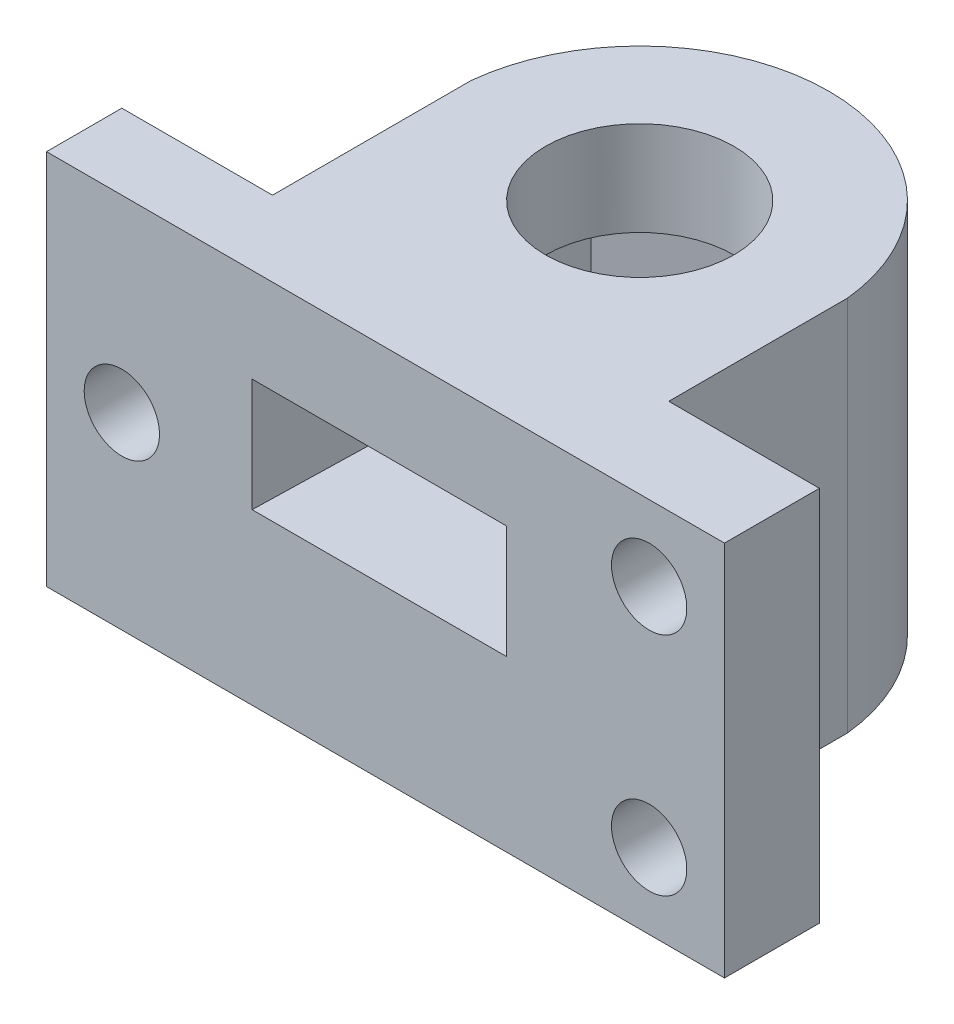
SolidWorks part; units mm, degrees
material "Copper"
ref_plane "Front Plane" through (0, 0, 0) normal (0, 0, 1) x (1, 0, 0)
ref_plane "Top Plane" through (0, 0, 0) normal (0, 1, 0) x (1, 0, 0)
ref_plane "Right Plane" through (0, 0, 0) normal (1, 0, 0) x (0, 0, -1)
sketch "Sketch1" plane through (0, 0, 0) normal (0, 1, 0) x (1, 0, 0)
  line L0 (0, 0) -> (20, 0)
  line L1 (0, 14.54) -> (0, 4)
  line L2 (20, 5.04) -> (20, 14.54)
  line L3 (0, 0) -> (-8, 0)
  line L4 (-8, 0) -> (-8, 4)
  line L5 (-8, 4) -> (0, 4)
  line L6 (20, 0) -> (28, 0)
  line L7 (28, 0) -> (28, 5.04)
  line L8 (28, 5.04) -> (20, 5.04)
  circle A0 centre (10, 13.5) radius 5
  arc A1 (0, 14.54) -> (20, 14.54) centre (10, 13.5) cw
  dimension "D1" = 13.5
  dimension "D2" = 9.5
  dimension "D3" = 10
extrude "Boss-Extrude1" add sketch "Sketch1" along normal blind 20
ref_plane "Plane1" through (0, 15, 0) normal (0, 1, 0) x (1, 0, 0)
sketch "Sketch4" plane through (0, 15, 0) normal (0, 1, 0) x (1, 0, 0)
  line L0 (10, 13.5) -> (10, -3.0938) construction
  line L2 (9.8055, 5.7082) -> (16.6507, 9.4357)
  line L3 (16.6507, 9.4357) -> (16.8451, 17.2275)
  line L4 (16.8451, 17.2275) -> (10.1945, 21.2918)
  line L5 (10.1945, 21.2918) -> (3.3493, 17.5643)
  line L6 (3.3493, 17.5643) -> (3.1549, 9.7725)
  line L7 (3.1549, 9.7725) -> (9.8055, 5.7082)
  circle A0 centre (10, 13.5) radius 6.75 construction
extrude "Cut-Extrude2" cut sketch "Sketch4" against normal blind 6
sketch "Sketch9" plane through (0, 0, -5.04) normal (0, 0, -1) x (-1, 0, 0)
  line L0 (-28, 20) -> (-28, 0) construction
  line L1 (-28, 0) -> (-20, 0) construction
  line L2 (-28, 20) -> (-20, 20) construction
  line L3 (8, 20) -> (8, 0) construction
  line L4 (0, 20) -> (8, 20) construction
  circle A0 centre (-24, 4) radius 2
  circle A1 centre (-24, 16) radius 2
  circle A2 centre (4, 10) radius 2
  dimension "D1" = 4
  dimension "D5" = 4
  dimension "D2" = 4
  dimension "D3" = 4
  dimension "D4" = 4
  dimension "D6" = 10
extrude "Cut-Extrude4" cut sketch "Sketch9" against normal blind 6
ref_plane "Plane7" through (0.2457, 0, -9.8451) normal (0.025, 0, -0.9997) x (-0.9997, 0, -0.025)
sketch "Sketch10" plane through (0.2457, 0, -9.8451) normal (0.025, 0, -0.9997) x (-0.9997, 0, -0.025)
  line L1 (-2.9173, 8.9958) -> (-16.4104, 8.9958)
  line L2 (-2.9173, 8.9958) -> (-2.9173, 15.0012)
  line L3 (-2.9173, 15.0012) -> (-16.4104, 15.0012)
  line L4 (-16.4104, 8.9958) -> (-16.4104, 15.0012)
extrude "Cut-Extrude5" cut sketch "Sketch10" against normal blind 10
